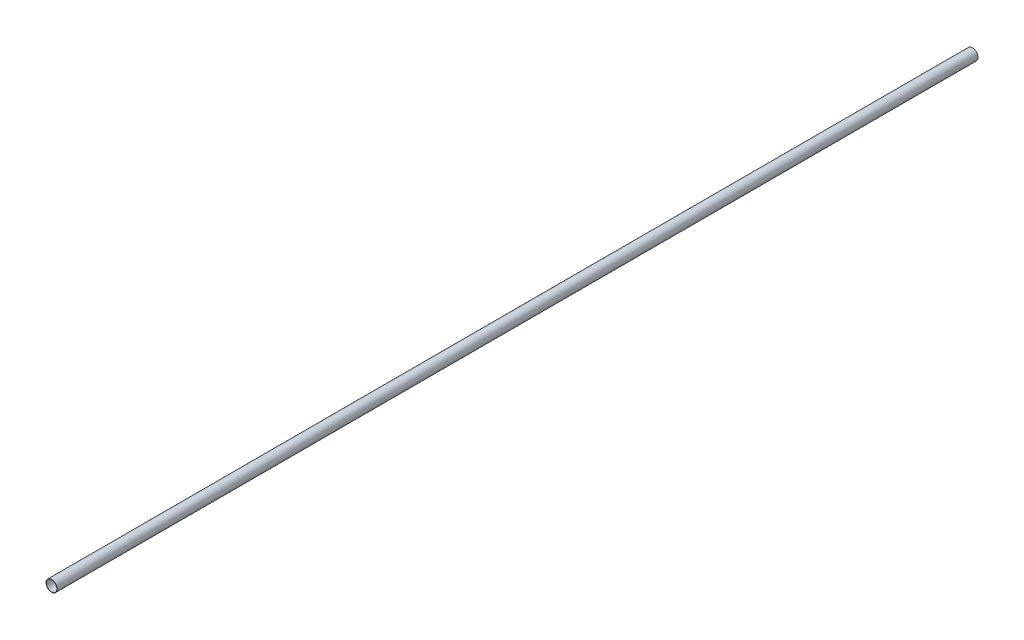
SolidWorks part; units mm, degrees
material "6061-T6 (SS)"
ref_plane "Front Plane" through (0, 0, 0) normal (0, 0, 1) x (1, 0, 0)
ref_plane "Top Plane" through (0, 0, 0) normal (0, 1, 0) x (1, 0, 0)
ref_plane "Right Plane" through (0, 0, 0) normal (1, 0, 0) x (0, 0, -1)
sketch "Sketch1" plane through (0, 0, 0) normal (0, 0, 1) x (1, 0, 0)
  circle A0 centre (-112.4201, -112.4201) radius 4.318
  circle A1 centre (-112.4201, -112.4201) radius 4.572
  dimension "D1" = 0.254
  dimension "D2" = 8.636
extrude "Boss-Extrude1" add sketch "Sketch1" along normal blind 755.65
